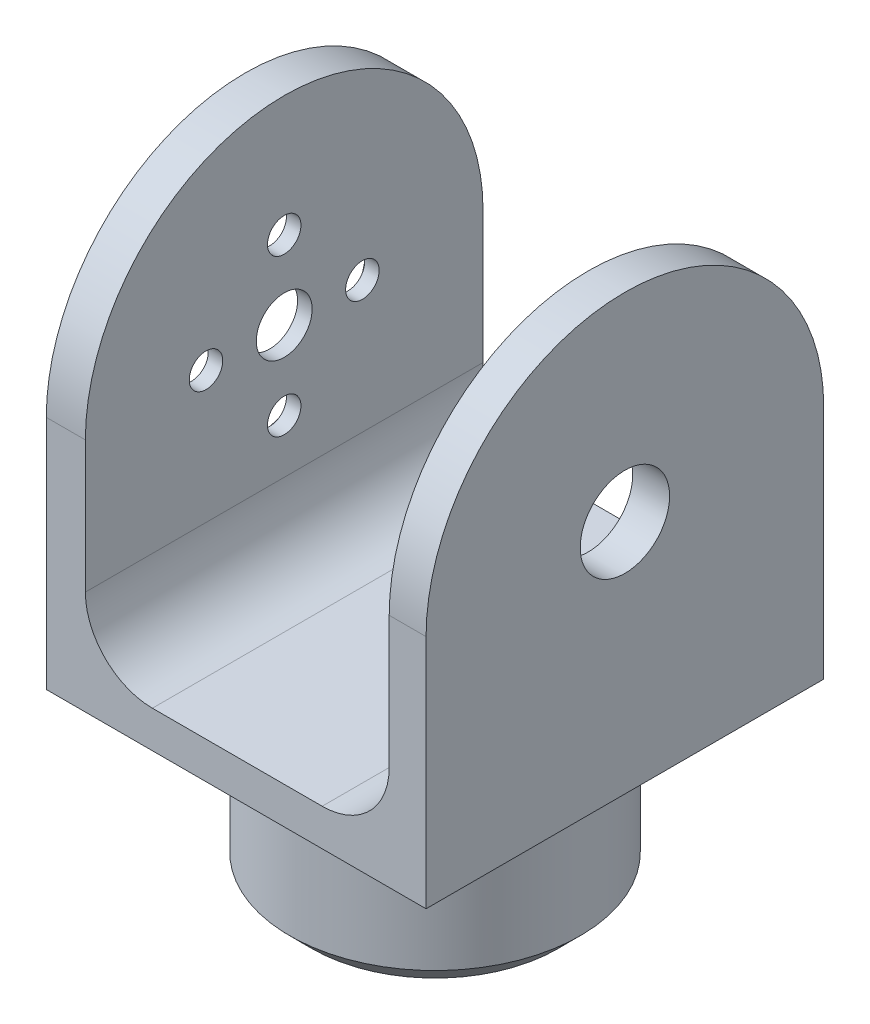
SolidWorks part; units mm, degrees
ref_plane "Front Plane" through (0, 0, 0) normal (0, 0, 1) x (1, 0, 0)
ref_plane "Top Plane" through (0, 0, 0) normal (0, 1, 0) x (1, 0, 0)
ref_plane "Right Plane" through (0, 0, 0) normal (1, 0, 0) x (0, 0, -1)
sketch "Sketch1" plane through (0, 0, 0) normal (0, 1, 0) x (1, 0, 0)
  line L1 (-17, -17.8) -> (17, -17.8)
  line L2 (-17, -17.8) -> (-17, 17.8)
  line L3 (-17, 17.8) -> (17, 17.8)
  line L4 (17, -17.8) -> (17, 17.8)
  line L5 (-17, -17.8) -> (17, 17.8) construction
  line L6 (-17, 17.8) -> (17, -17.8) construction
  point P0 (0, 0)
  dimension "D1" = 35.6
  dimension "D2" = 34
extrude "Boss-Extrude1" add sketch "Sketch1" along normal blind 3.3
sketch "Sketch3" plane through (-17, 0, 0) normal (-1, 0, 0) x (0, 0, 1)
  line L0 (0, 0) -> (0, 38.9) construction
  line L1 (-17.8, 3.3) -> (-17.8, 21.1)
  line L2 (17.8, 3.3) -> (17.8, 21.1)
  line L3 (-17.8, 3.3) -> (18.167, 3.3)
  arc A0 (-17.8, 21.1) -> (17.8, 21.1) centre (0, 21.1) cw
  line M3 (17.8, 3.3) -> (-17.8, 3.3)
  dimension "D1" = 17.8
extrude "Boss-Extrude2" add sketch "Sketch3" against normal blind 3.5 contours L0 L2 A0 M3 | L3 L0 A0 L1 region at (-17, 19.4384, -8.3081) region at (-17, 19.4384, 8.3081)
extrude "Boss-Extrude3" add sketch "Sketch3<4>" along normal blind 3.3 from surface contours L3 L0 A0 L1 | L0 L2 A0 M3 region at (-17, 19.4384, -8.3081) region at (-17, 19.4384, 8.3081) starting at face at (17, 1.65, 0)
sketch "Sketch3<4>" plane through (-17, 0, 0) normal (-1, 0, 0) x (0, 0, 1) same geometry as "Sketch3"
sketch "Sketch4" plane through (-17, 0, 0) normal (-1, 0, 0) x (0, 0, 1)
  line L0 (0, 38.9) -> (0, 0) construction
  line L1 (-17.8, 0) -> (17.8, 0) construction
  line L2 (-10.925, 21.1) -> (10.925, 21.1) construction
  circle A0 centre (0, 21.1) radius 10.925
  arc A1 (17.8, 21.1) -> (-17.8, 21.1) centre (0, 21.1) ccw construction
  circle A2 centre (0, 28.1) radius 1.5
  circle A3 centre (0, 14.1) radius 1.5
  circle A4 centre (-7, 21.1) radius 1.5
  circle A5 centre (7, 21.1) radius 1.5
  circle A6 centre (0, 21.1) radius 2.5
  dimension "D1" = 21.85
  dimension "D2" = 3
  dimension "D3" = 3
  dimension "D4" = 3
  dimension "D5" = 3
  dimension "D6" = 5
  dimension "D7" = 7
  dimension "D8" = 7
  dimension "D9" = 7
  dimension "D10" = 7
extrude "Cut-Extrude1" cut sketch "Sketch4" against normal blind 12 contours A6 | A5 | A2 | A4 | A3 region at (-17, 28.1, 0) region at (-17, 14.1, 0) region at (-17, 21.1, -7) region at (-17, 21.1, 7) region at (-17, 21.1, 0)
extrude "Cut-Extrude2" cut sketch "Sketch4<3>" against normal blind 2.2
sketch "Sketch4<3>" plane through (-17, 0, 0) normal (-1, 0, 0) x (0, 0, 1) same geometry as "Sketch4"
sketch "Sketch5" plane through (17, 0, 0) normal (1, 0, 0) x (0, 0, -1)
  line L0 (0, 38.9) -> (0, 0) construction
  arc A0 (17.8, 21.1) -> (-17.8, 21.1) centre (0, 21.1) ccw construction
  circle A1 centre (0, 21.1) radius 4
  dimension "D1" = 8
extrude "Cut-Extrude3" cut sketch "Sketch5" against normal blind 12.2
sketch "Sketch6" plane through (0, 0, 0) normal (0, -1, 0) x (1, 0, 0)
  circle A0 centre (0, 0) radius 2.5
  dimension "D1" = 5
extrude "Cut-Extrude4" cut sketch "Sketch6" against normal through all both and the other way through all
fillet "Fillet1" radius 6 2 edges at (13.7, 3.3, 0) (-13.5, 3.3, 0)
sketch "Sketch7" plane through (0, 0, 0) normal (0, -1, 0) x (1, 0, 0)
  circle A0 centre (0, 0) radius 10 construction
  circle A1 centre (0, 0) radius 11
  circle A2 centre (0, 0) radius 13
  dimension "D1" = 20
  dimension "D2" = 1
  dimension "D3" = 2
extrude "Boss-Extrude4" add sketch "Sketch7" along normal blind 15
chamfer "Chamfer1" distance 2 angle 45 1 edges at (0, -15, -13)
fillet "Fillet2" radius 3 1 edges at (0, 0, -13)
sketch "Sketch9" plane through (0, 0, -17.8) normal (0, 0, -1) x (-1, 0, 0)
  line L0 (0, 0) -> (0, -15) construction
  line L1 (-11, -15) -> (11, -15) construction
  line L2 (-16, 0) -> (16, 0) construction
  circle A0 centre (0, -2.5) radius 2.5
  dimension "D1" = 5
extrude "Cut-Extrude5" cut sketch "Sketch9" against normal blind 15
